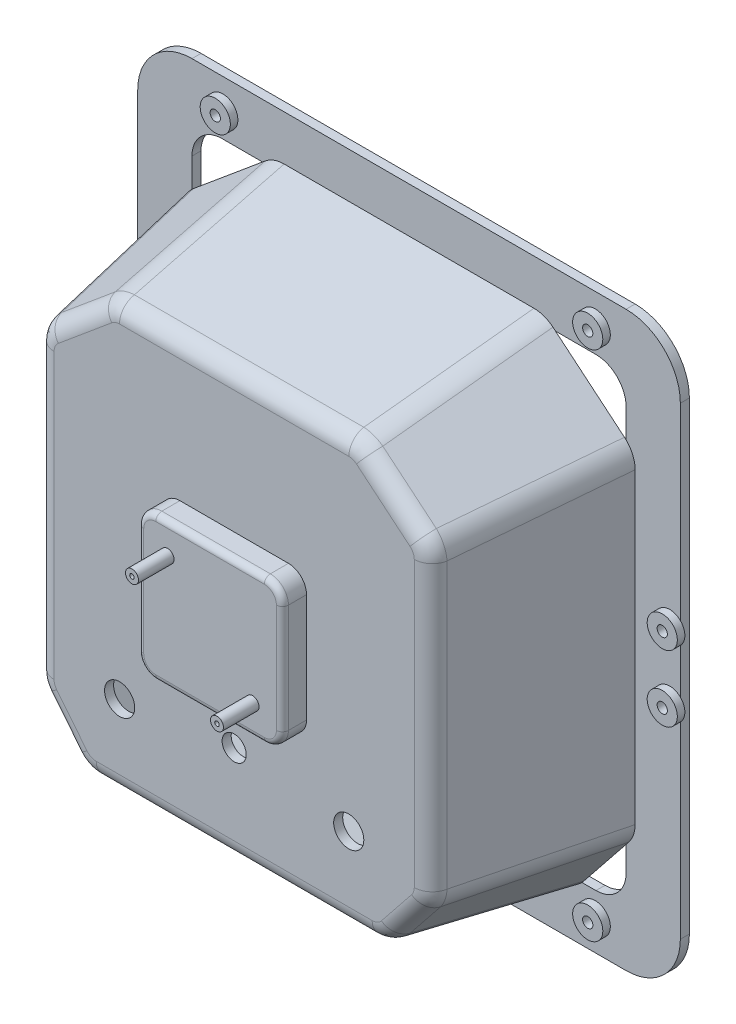
SolidWorks part; units mm, degrees
ref_plane "Front Plane" through (0, 0, 0) normal (0, 0, 1) x (1, 0, 0)
ref_plane "Top Plane" through (0, 0, 0) normal (0, 1, 0) x (1, 0, 0)
ref_plane "Right Plane" through (0, 0, 0) normal (1, 0, 0) x (0, 0, -1)
sketch "SK_Brim_180x190" plane through (0, 0, 0) normal (0, 0, 1) x (1, 0, 0)
  line L1 (-90, -95) -> (90, -95)
  line L2 (-90, -95) -> (-90, 95)
  line L3 (-90, 95) -> (90, 95)
  line L4 (90, -95) -> (90, 95)
  line L5 (-72, -77) -> (72, -77)
  line L6 (-72, -77) -> (-72, 77)
  line L7 (-72, 77) -> (72, 77)
  line L8 (72, -77) -> (72, 77)
extrude "Board_Mount_Brim_3mm" add sketch "SK_Brim_180x190" along normal blind 3
fillet "Brim_Outer_R18" radius 18 4 edges at (-90, 95, 1.5) (90, 95, 1.5) (90, -95, 1.5) (-90, -95, 1.5)
fillet "Brim_Inner_R10" radius 10 4 edges at (-72, 77, 1.5) (72, 77, 1.5) (72, -77, 1.5) (-72, -77, 1.5)
sketch "SK_UpperBoard_8X_M3" plane through (0, 0, 3) normal (0, 0, 1) x (1, 0, 0)
  circle A0 centre (-86.5, -11) radius 1.7
  circle A1 centre (-86.5, 11) radius 1.7
  circle A2 centre (86.5, -11) radius 1.7
  circle A3 centre (86.5, 11) radius 1.7
  circle A4 centre (-61.7761, -84.9997) radius 1.7
  circle A5 centre (61.7761, -84.9997) radius 1.7
  circle A6 centre (-61.7761, 84.9997) radius 1.7
  circle A7 centre (61.7761, 84.9997) radius 1.7
extrude "UpperBoard_M3_Clearance_8X" cut sketch "SK_UpperBoard_8X_M3" against normal blind 3.2
sketch "SK_Cockpit_Octagon" plane through (0, 0, 3) normal (0, 0, 1) x (1, 0, 0)
  line L0 (-55, -80) -> (55, -80)
  line L1 (55, -80) -> (75, -55)
  line L2 (75, -55) -> (75, 55)
  line L3 (75, 55) -> (45, 80)
  line L4 (45, 80) -> (-45, 80)
  line L5 (-45, 80) -> (-75, 55)
  line L6 (-75, 55) -> (-75, -55)
  line L7 (-75, -55) -> (-55, -80)
extrude "Cockpit_Canopy_Draft10deg" add sketch "SK_Cockpit_Octagon" along normal blind 58 draft 10
fillet "Canopy_Corners_R10" radius 10 8 edges at (-69.8865, -53.2063, 32) (-69.8865, 52.605, 32) (-43.1487, 74.8865, 32) (43.1487, 74.8865, 32) (69.8865, 52.605, 32) (69.8865, -53.2063, 32) (52.5423, -74.8865, 32) (-52.5423, -74.8865, 32)
fillet "Canopy_Roof_R6" radius 6 16 edges at (-57.8283, -60.0936, 61) (0, -69.773, 61) (57.8283, -60.0936, 61) (64.773, -1.1804, 61) (52.633, 60.3267, 61) (0, 69.773, 61) (-52.633, 60.3267, 61) (-64.773, -1.1804, 61) (-49.6183, -68.8027, 61) (49.6183, -68.8027, 61) (64.2184, -51.218, 61) (63.8447, 49.7752, 61) (41.0846, 69.1854, 61) (-41.0846, 69.1854, 61) (-63.8447, 49.7752, 61) (-64.2184, -51.218, 61)
sketch "SK_Symmetric_Cavity" plane through (0, 0, 0) normal (0, 0, -1) x (-1, 0, 0)
  line L0 (-53, -77) -> (53, -77)
  line L1 (57.3444, -77) -> (-57.3444, -77) construction
  line L2 (53, -77) -> (72, -52)
  line L3 (72, 57.4649) -> (72, -58.75) construction
  line L4 (72, -52) -> (72, 52)
  line L5 (72, 52) -> (43, 77)
  line L6 (-62, 77) -> (62, 77) construction
  line L7 (43, 77) -> (-43, 77)
  line L8 (-43, 77) -> (-72, 52)
  line L9 (-72, -67) -> (-72, 67) construction
  line L10 (-72, 52) -> (-72, -52)
  line L11 (-72, -52) -> (-53, -77)
extrude "Symmetric_Electronics_Cavity_58H" cut sketch "SK_Symmetric_Cavity" against normal blind 58 draft 10
sketch "SK_LD06_RaisedPad" plane through (0, 0, 61) normal (0, 0, 1) x (1, 0, 0)
  line L1 (-24, -24) -> (24, -24)
  line L2 (-24, -24) -> (-24, 24)
  line L3 (-24, 24) -> (24, 24)
  line L4 (24, -24) -> (24, 24)
extrude "LD06_Raised_Platform_8mm" add sketch "SK_LD06_RaisedPad" along normal blind 8
fillet "LD06_Platform_Corners_R6" radius 6 4 edges at (-24, 24, 65) (24, 24, 65) (24, -24, 65) (-24, -24, 65)
fillet "LD06_Platform_Top_R2" radius 2 8 edges at (-24, 0, 69) (0, -24, 69) (24, 0, 69) (0, 24, 69) (-22.2426, -22.2426, 69) (22.2426, -22.2426, 69) (22.2426, 22.2426, 69) (-22.2426, 22.2426, 69)
sketch "SK_LD06_PiBracket_Columns" plane through (0, 0, 69) normal (0, 0, 1) x (1, 0, 0)
  circle A0 centre (-14.1, 14.1) radius 2.15
  circle A1 centre (14.1, -14.1) radius 2.15
extrude "LD06_Fixing_Columns_D4p3_H11p8" add sketch "SK_LD06_PiBracket_Columns" along normal blind 11.8
sketch "SK_LD06_Pilot_Holes" plane through (0, 0, 80.8) normal (0, 0, 1) x (1, 0, 0)
  circle A0 centre (-14.1, 14.1) radius 0.75
  circle A1 centre (14.1, -14.1) radius 0.75
extrude "LD06_Pilots_D1p5_11p3Deep" cut sketch "SK_LD06_Pilot_Holes" against normal blind 11.3
sketch "SK_Roof_Cable_Ports" plane through (0, 0, 61) normal (0, 0, 1) x (1, 0, 0)
  circle A0 centre (-38, -43) radius 5
  circle A1 centre (38, -43) radius 5
  circle A2 centre (0, -38) radius 4
extrude "Roof_GPS2_UART_Cable_Ports" cut sketch "SK_Roof_Cable_Ports" against normal blind 4
sketch "SK_Brim_Reinforcement_Pads" plane through (0, 0, 3) normal (0, 0, 1) x (1, 0, 0)
  circle A0 centre (-86.5, -11) radius 5
  circle A1 centre (-86.5, -11) radius 1.7
  circle A2 centre (-86.5, 11) radius 5
  circle A3 centre (-86.5, 11) radius 1.7
  circle A4 centre (86.5, -11) radius 5
  circle A5 centre (86.5, -11) radius 1.7
  circle A6 centre (86.5, 11) radius 5
  circle A7 centre (86.5, 11) radius 1.7
  circle A8 centre (-61.7761, -84.9997) radius 5
  circle A9 centre (-61.7761, -84.9997) radius 1.7
  circle A10 centre (61.7761, -84.9997) radius 5
  circle A11 centre (61.7761, -84.9997) radius 1.7
  circle A12 centre (-61.7761, 84.9997) radius 5
  circle A13 centre (-61.7761, 84.9997) radius 1.7
  circle A14 centre (61.7761, 84.9997) radius 5
  circle A15 centre (61.7761, 84.9997) radius 1.7
extrude "Brim_M3_Reinforcement_Pads_8X" add sketch "SK_Brim_Reinforcement_Pads" along normal blind 2.5
